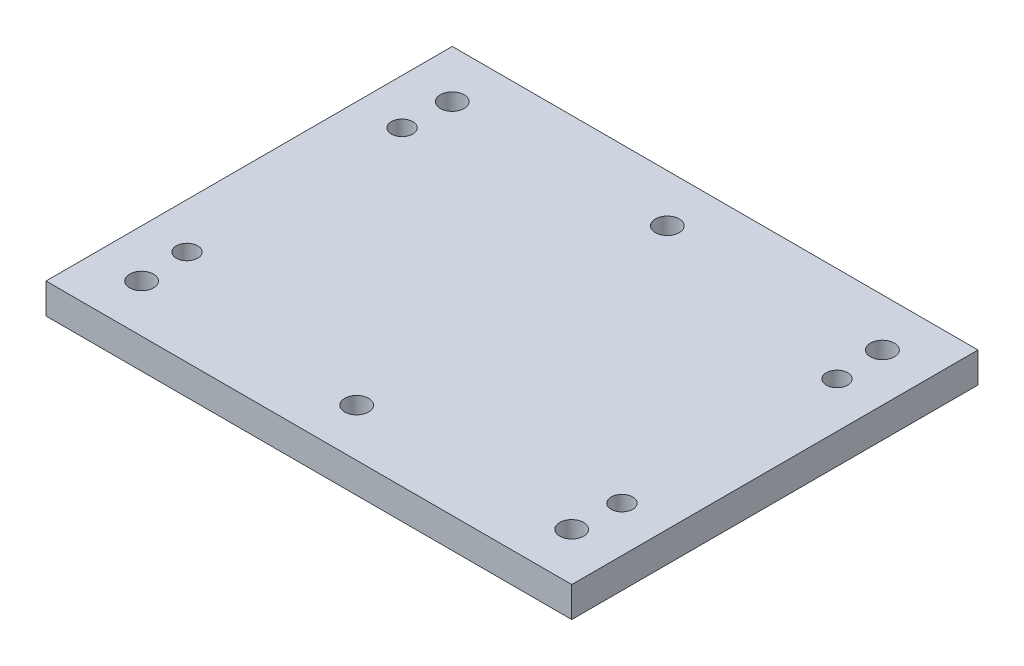
SolidWorks part; units mm, degrees
ref_plane "Front Plane" through (0, 0, 0) normal (0, 0, 1) x (1, 0, 0)
ref_plane "Top Plane" through (0, 0, 0) normal (0, 1, 0) x (1, 0, 0)
ref_plane "Right Plane" through (0, 0, 0) normal (1, 0, 0) x (0, 0, -1)
sketch "Sketch1" plane through (0, 0, 0) normal (0, 1, 0) x (1, 0, 0)
  line L0 (0, -2.75) -> (0, 2.75) construction
  line L1 (-55, 42.5) -> (55, 42.5)
  line L2 (-55, 42.5) -> (-55, -42.5)
  line L3 (-55, -42.5) -> (55, -42.5)
  line L4 (55, 42.5) -> (55, -42.5)
  line L5 (-55, 42.5) -> (55, -42.5) construction
  line L6 (-55, -42.5) -> (55, 42.5) construction
  line L7 (-45.5, 22.5) -> (45.5, 22.5) construction
  line L8 (-45.5, 22.5) -> (-45.5, -22.5) construction
  line L9 (-45.5, -22.5) -> (45.5, -22.5) construction
  line L10 (45.5, 22.5) -> (45.5, -22.5) construction
  line L11 (-45.5, 22.5) -> (45.5, -22.5) construction
  line L12 (-45.5, -22.5) -> (45.5, 22.5) construction
  line L13 (-2.75, 0) -> (2.75, 0) construction
  line L14 (45, -42.5) -> (45, -32.5) construction
  line L16 (-45, 32.5) -> (45, 32.5) construction
  line L17 (-45, 32.5) -> (-45, -32.5) construction
  line L18 (-45, -32.5) -> (45, -32.5) construction
  line L19 (45, 32.5) -> (45, -32.5) construction
  line L20 (-45, 32.5) -> (45, -32.5) construction
  line L21 (-45, -32.5) -> (45, 32.5) construction
  circle A0 centre (-45.5, 22.5) radius 2.25
  circle A1 centre (45.5, 22.5) radius 2.25
  circle A2 centre (45.5, -22.5) radius 2.25
  circle A3 centre (-45.5, -22.5) radius 2.25
  circle A4 centre (45, -32.5) radius 2.5
  circle A5 centre (-45, -32.5) radius 2.5
  circle A6 centre (-45, 32.5) radius 2.5
  circle A7 centre (45, 32.5) radius 2.5
  circle A8 centre (0, -32.5) radius 2.5
  circle A9 centre (0, 32.5) radius 2.5
  point P0 (0, 0)
  point P6 (0, 0)
  point P28 (0, 0)
  dimension "D5" = 4.5
  dimension "D6" = 5
  dimension "D11" = 5
  dimension "D12" = 5
  dimension "D1" = 110
  dimension "D2" = 85
  dimension "D3" = 45
  dimension "D4" = 91
  dimension "D7" = 10
  dimension "D8" = 10
  dimension "D9" = 90
  dimension "D10" = 65
extrude "Boss-Extrude1" add sketch "Sketch1" along normal blind 3.175 and the other way blind 3.175
